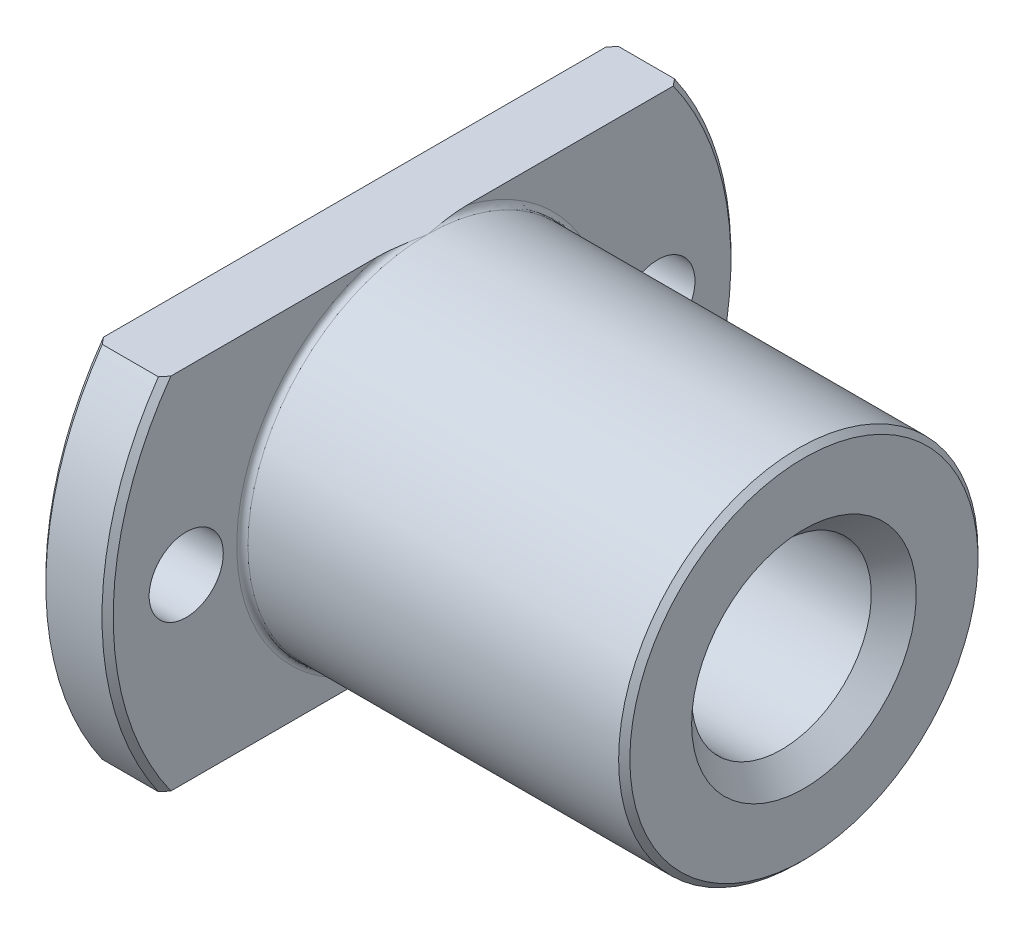
SolidWorks part; units mm, degrees
ref_plane "前视基准面" through (0, 0, 0) normal (0, 0, 1) x (1, 0, 0)
ref_plane "上视基准面" through (0, 0, 0) normal (0, 1, 0) x (1, 0, 0)
ref_plane "右视基准面" through (0, 0, 0) normal (1, 0, 0) x (0, 0, -1)
sketch "草图1" plane through (0, 0, 0) normal (0, 0, 1) x (1, 0, 0)
  line L0 (0, 0) -> (0, 27.5)
  line L1 (0, 27.5) -> (0.5, 28)
  line L2 (0.5, 28) -> (5.5, 28)
  line L3 (5.5, 28) -> (6, 27.5)
  line L4 (6, 27.5) -> (6, 16.5)
  line L5 (6.5, 16) -> (39.5, 16)
  line L6 (39.5, 16) -> (40, 15.5)
  line L7 (40, 15.5) -> (40, 0)
  line L8 (40, 0) -> (0, 0)
  line L9 (40, 0) -> (0, 0) construction
  arc A0 (6, 16.5) -> (6.5, 16) centre (6.5, 16.5) ccw
revolve "旋转1" add sketch "草图1" angle 360 about L9 reverse direction yes
sketch "草图2" plane through (0, 0, 0) normal (0, 0, 1) x (1, 0, 0)
  line L0 (0, 0) -> (0, 10)
  line L1 (0, 10) -> (2, 8)
  line L2 (2, 8) -> (38, 8)
  line L3 (38, 8) -> (40, 10)
  line L4 (40, 10) -> (40, 0)
  line L5 (40, 0) -> (0, 0)
  line L6 (40, 0) -> (0, 0) construction
revolve "切除-旋转1" cut sketch "草图2" angle 360 about L6 reverse direction yes
cosmetic thread "装饰螺纹线1" parameters "D1"=40, "D2"=20
sketch "草图3" plane through (0, 0, 0) normal (1, 0, 0) x (0, 0, -1)
  circle A0 centre (21, 0) radius 3.3
extrude "切除-拉伸1" cut sketch "草图3" along normal blind 6
sketch "草图4" plane through (0, 0, 0) normal (1, 0, 0) x (0, 0, -1)
  circle A0 centre (-21, 0) radius 3.3
extrude "切除-拉伸2" cut sketch "草图4" along normal blind 6
sketch "草图5" plane through (0, 0, 0) normal (1, 0, 0) x (0, 0, -1)
  circle A0 centre (0, 21) radius 3.3
extrude "切除-拉伸3" cut sketch "草图5" along normal blind 6
sketch "草图6" plane through (0, 0, 0) normal (1, 0, 0) x (0, 0, -1)
  circle A0 centre (0, -21) radius 3.3
extrude "切除-拉伸4" cut sketch "草图6" along normal blind 6
sketch "草图7" plane through (0, 0, 0) normal (0, 0, 1) x (1, 0, 0)
  line L0 (0, 16) -> (40, 16)
  line L1 (40, 16) -> (40, 48)
  line L2 (40, 48) -> (0, 48)
  line L3 (0, 48) -> (0, 16)
extrude "切除-拉伸5" cut sketch "草图7" along normal blind 42 and the other way blind 42
sketch "草图8" plane through (0, 0, 0) normal (0, 0, 1) x (1, 0, 0)
  line L0 (0, -16) -> (0, -48)
  line L1 (0, -48) -> (40, -48)
  line L2 (40, -48) -> (40, -16)
  line L3 (40, -16) -> (0, -16)
extrude "切除-拉伸6" cut sketch "草图8" along normal blind 42 and the other way blind 42
ref_plane "to_kue XY" through (0, 0, 0) normal (1, 0, 0) x (0, 0, -1)
ref_plane "to_kue XZ" through (0, 0, 0) normal (0, -1, 0) x (-1, 0, 0)
ref_plane "to_kue YZ" through (0, 0, 0) normal (0, 0, -1) x (-1, 0, 0)
ref_axis "to_kue X" through (0, 0, 80.9) along (0, 0, -1)
ref_axis "to_kue Y" through (0, -50, 0) along (0, 1, 0)
ref_axis "to_kue Z" through (80.9, 0, 0) along (-1, 0, 0)
sketch3d "to_kue"
  point P0 (0, 0, 0)
ref_plane "nut_to_kue 1 XY" through (0, 0, 0) normal (1, 0, 0) x (0, 0, -1)
ref_plane "nut_to_kue 1 XZ" through (0, 0, 0) normal (0, -1, 0) x (-1, 0, 0)
ref_plane "nut_to_kue 1 YZ" through (0, 0, 21) normal (0, 0, -1) x (-1, 0, 0)
ref_axis "nut_to_kue 1 X" through (0, 0, 80.9) along (0, 0, -1)
ref_axis "nut_to_kue 1 Y" through (0, -50, 21) along (0, 1, 0)
ref_axis "nut_to_kue 1 Z" through (80.9, 0, 21) along (-1, 0, 0)
sketch3d "nut_to_kue 1"
  point P0 (0, 0, 21)
ref_plane "nut_to_kue 2 XY" through (0, 0, 0) normal (1, 0, 0) x (0, 0, -1)
ref_plane "nut_to_kue 2 XZ" through (0, 0, 0) normal (0, -1, 0) x (-1, 0, 0)
ref_plane "nut_to_kue 2 YZ" through (0, 0, -21) normal (0, 0, -1) x (-1, 0, 0)
ref_axis "nut_to_kue 2 X" through (0, 0, 80.9) along (0, 0, -1)
ref_axis "nut_to_kue 2 Y" through (0, -50, -21) along (0, 1, 0)
ref_axis "nut_to_kue 2 Z" through (80.9, 0, -21) along (-1, 0, 0)
sketch3d "nut_to_kue 2"
  point P0 (0, 0, -21)
